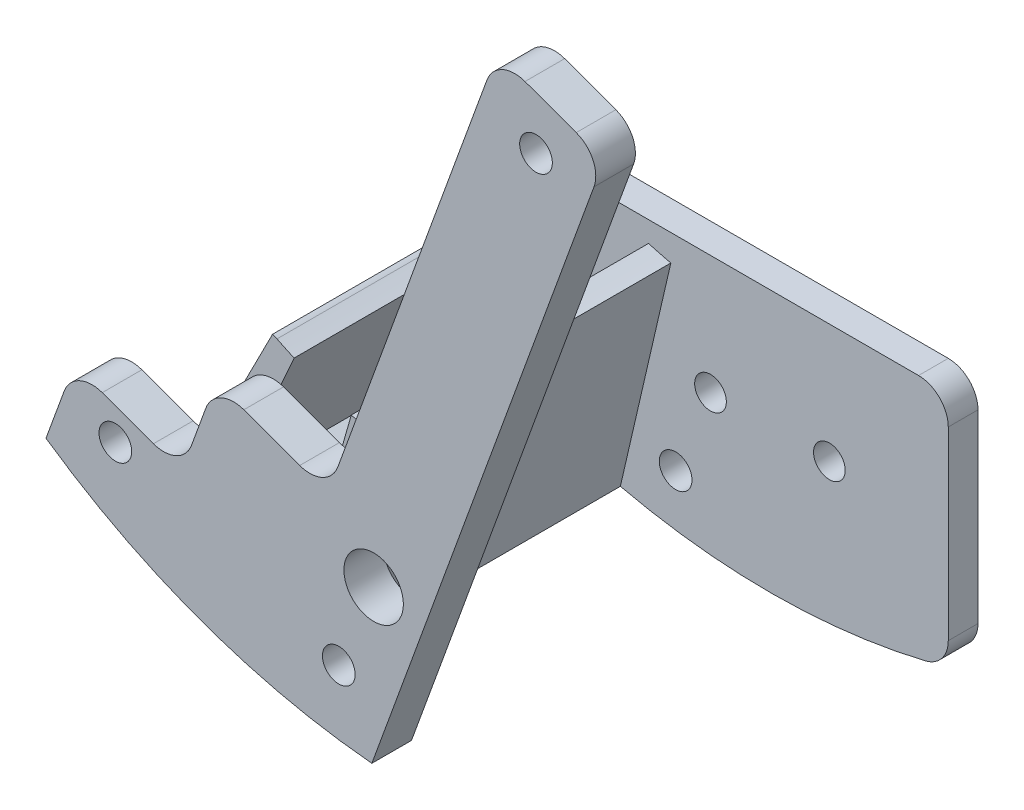
SolidWorks part; units mm, degrees
ref_plane "前视基准面" through (0, 0, 0) normal (0, 0, 1) x (1, 0, 0)
ref_plane "上视基准面" through (0, 0, 0) normal (0, 1, 0) x (1, 0, 0)
ref_plane "右视基准面" through (0, 0, 0) normal (1, 0, 0) x (0, 0, -1)
sketch "草图1" plane through (0, 0, 0) normal (0, 0, 1) x (1, 0, 0)
  line L0 (9.9767, -14.6317) -> (9.9767, -38.6317) construction
  line L1 (-8.0233, -14.6317) -> (27.9767, -14.6317)
  line L3 (-8.0233, -38.6317) -> (27.9767, -38.6317)
  line L4 (27.9767, -14.6317) -> (27.9767, -38.6317)
  line L5 (-43.0233, 26.0276) -> (62.9767, 26.0276) construction
  line L7 (-34.4888, 26.0276) -> (-57.1413, 26.0276)
  circle A0 centre (3.9767, -26.6317) radius 1.6
  circle A1 centre (15.9767, -26.6317) radius 1.6
  circle A2 centre (9.9767, 26.0276) radius 53 construction
  arc A3 (-57.1413, 26.0276) -> (-8.0233, -38.6317) centre (9.9767, 26.0276) ccw
  arc A4 (-34.4888, 26.0276) -> (-8.0233, -14.6317) centre (9.9767, 26.0276) ccw
  circle A5 centre (-42.6826, 20.0276) radius 1.6
  dimension "D1" = 3.2
  dimension "D2" = 6
  dimension "D5" = 12
  dimension "D6" = 106
  dimension "D8" = 6
  dimension "D9" = 3.2
  dimension "D3" = 36
  dimension "D4" = 24
extrude "凸台-拉伸1" add sketch "草图1" along normal blind 3
sketch "草图2" plane through (0, 0, 3) normal (0, 0, 1) x (1, 0, 0)
  line L0 (-34.4888, 26.0276) -> (-57.1413, 26.0276) construction
  line L1 (9.9767, 26.0276) -> (-12.979, -37.0427) construction
  line L2 (9.9767, 26.0276) -> (-5.1216, -39.3702) construction
  line L3 (9.9767, 26.0276) -> (-20.4942, -33.775) construction
  line L4 (-20.4942, -33.775) -> (-10.2102, -13.5914)
  line L5 (-0.0259, -17.2982) -> (-5.1216, -39.3702)
  arc A0 (-10.2102, -13.5914) -> (-0.0259, -17.2982) centre (9.9767, 26.0276) ccw
  arc A1 (-20.4942, -33.775) -> (-5.1216, -39.3702) centre (9.9767, 26.0276) ccw
  dimension "D1" = 70
  dimension "D2" = 7
  dimension "D3" = 7
extrude "凸台-拉伸2" add sketch "草图2" along normal blind 30
ref_plane "基准面1" through (0, 0, 3) normal (0, 0, 1) x (1, 0, 0)
sketch "草图3" plane through (0, 0, 3) normal (0, 0, 1) x (1, 0, 0)
  line L0 (-12.979, -37.0427) -> (-5.2314, -15.7563) construction
  line L1 (9.9767, 26.0276) -> (-6.5616, -31.6481) construction
  line L2 (-14.3487, -28.8202) -> (-7.4565, -13.28)
  line L3 (-1.8757, -15.3067) -> (-6.5616, -31.6481)
  line L4 (-4.9511, -38.6317) -> (-0.0259, -17.2982) construction
  line L5 (9.9767, 26.0276) -> (-14.3487, -28.8202) construction
  line L6 (-10.2102, -13.5914) -> (-20.4942, -33.775) construction
  arc A0 (-20.4942, -33.775) -> (-5.1216, -39.3702) centre (9.9767, 26.0276) ccw construction
  arc A1 (-10.2102, -13.5914) -> (-0.0259, -17.2982) centre (9.9767, 26.0276) ccw construction
  arc A2 (-7.4565, -13.28) -> (-1.8757, -15.3067) centre (9.9767, 26.0276) ccw
  arc A3 (-14.3487, -28.8202) -> (-6.5616, -31.6481) centre (9.9767, 26.0276) ccw
  point P14 (-15.3522, -23.6832)
  dimension "D3" = 43
  dimension "D4" = 60
  dimension "D1" = 3
  dimension "D2" = 3
extrude "切除-拉伸1" cut sketch "草图3" along normal blind 40
sketch "草图4" plane through (0, 0, 33) normal (0, 0, 1) x (1, 0, 0)
  line L0 (-12.979, -37.0427) -> (9.9767, 26.0276) construction
  line L1 (-27.8784, -26.8118) -> (5.0109, -38.7825)
  line L2 (5.0109, -38.7825) -> (27.2422, 22.2976)
  line L3 (27.2422, 22.2976) -> (16.4357, 26.2308)
  line L4 (-26.2367, -22.3012) -> (-27.8784, -26.8118)
  line L5 (4.0898, -25.232) -> (20.3638, 19.4802) construction
  line L6 (-0.6653, -20.7538) -> (16.4357, 26.2308)
  line L7 (-0.6653, -20.7538) -> (-11.9416, -16.6496)
  line L8 (-11.9416, -16.6496) -> (-15.4302, -26.2345)
  line L9 (-15.4302, -26.2345) -> (-26.2367, -22.3012)
  circle A1 centre (9.9767, 26.0276) radius 65 construction
  circle A2 centre (20.3638, 19.4802) radius 1.65
  circle A3 centre (0.4582, -35.2099) radius 1.65
  circle A4 centre (-22.0944, -27.0014) radius 1.65
  arc A5 (-20.4942, -33.775) -> (-5.1216, -39.3702) centre (9.9767, 26.0276) ccw construction
  arc A6 (-57.1413, 26.0276) -> (-20.4942, -33.775) centre (9.9767, 26.0276) ccw construction
  point P23 (-12.979, -37.0427)
  dimension "D1" = 130
  dimension "D6" = 3.3
  dimension "D7" = 5
  dimension "D8" = 3.3
  dimension "D9" = 58.2
  dimension "D13" = 3
  dimension "D2" = 35
  dimension "D4" = 65
  dimension "D5" = 12
  dimension "D10" = 50
  dimension "D11" = 6
  dimension "D12" = 12
extrude "凸台-拉伸3" add sketch "草图4" along normal blind 4
sketch "草图7" plane through (0, 0, 3) normal (0, 0, 1) x (1, 0, 0)
  line L0 (-12.2561, -12.4806) -> (-23.5823, -32.0983)
  line L1 (-34.4888, 26.0276) -> (-57.1413, 26.0276)
  arc A0 (-34.4888, 26.0276) -> (-12.2561, -12.4806) centre (9.9767, 26.0276) ccw
  arc A1 (-57.1413, 26.0276) -> (-23.5823, -32.0983) centre (9.9767, 26.0276) ccw
  dimension "D1" = 60
extrude "切除-拉伸5" cut sketch "草图7" against normal blind 3
sketch "草图8" plane through (0, 0, 0) normal (0, 0, -1) x (-1, 0, 0)
  line L0 (-27.9767, -38.6317) -> (8.0233, -38.6317)
  arc A0 (-27.9767, -38.6317) -> (8.0233, -38.6317) centre (-9.9767, 26.0276) ccw
extrude "凸台-拉伸4" add sketch "草图8" against normal blind 3
fillet "圆角2" radius 3 10 edges at (27.2422, 22.2976, 35) (16.4357, 26.2308, 35) (-0.6653, -20.7538, 35) (-15.4302, -26.2345, 35) (-11.9416, -16.6496, 35) (-26.2367, -22.3012, 35) (27.9767, -38.6317, 1.5) (27.9767, -14.6317, 1.5) (-12.2561, -12.4806, 1.5) (-23.5823, -32.0983, 1.5)
sketch "草图9" plane through (0, 0, 37) normal (0, 0, 1) x (1, 0, 0)
  line L0 (-27.8784, -26.8118) -> (-29.0942, -30.1521)
  line L1 (5.0109, -38.7825) -> (3.7951, -42.1228)
  line L3 (-27.8784, -26.8118) -> (5.0109, -38.7825)
  arc A0 (-29.0942, -30.1521) -> (3.7951, -42.1228) centre (9.9767, 26.0276) ccw
extrude "凸台-拉伸5" add sketch "草图9" against normal blind 4
sketch "草图10" plane through (0, 0, 37) normal (0, 0, 1) x (1, 0, 0)
  circle A0 centre (3.9767, -26.6317) radius 3
  circle A1 centre (15.9767, -26.6317) radius 1.6 construction
  dimension "D1" = 12
  dimension "D3" = 6
  dimension "D2" = 0
extrude "切除-拉伸6" cut sketch "草图10" against normal blind 4
sketch "草图11" plane through (0, 0, 3) normal (0, 0, 1) x (1, 0, 0)
  circle A0 centre (0.4582, -35.2099) radius 1.65
extrude "切除-拉伸7" cut sketch "草图11" against normal through all
